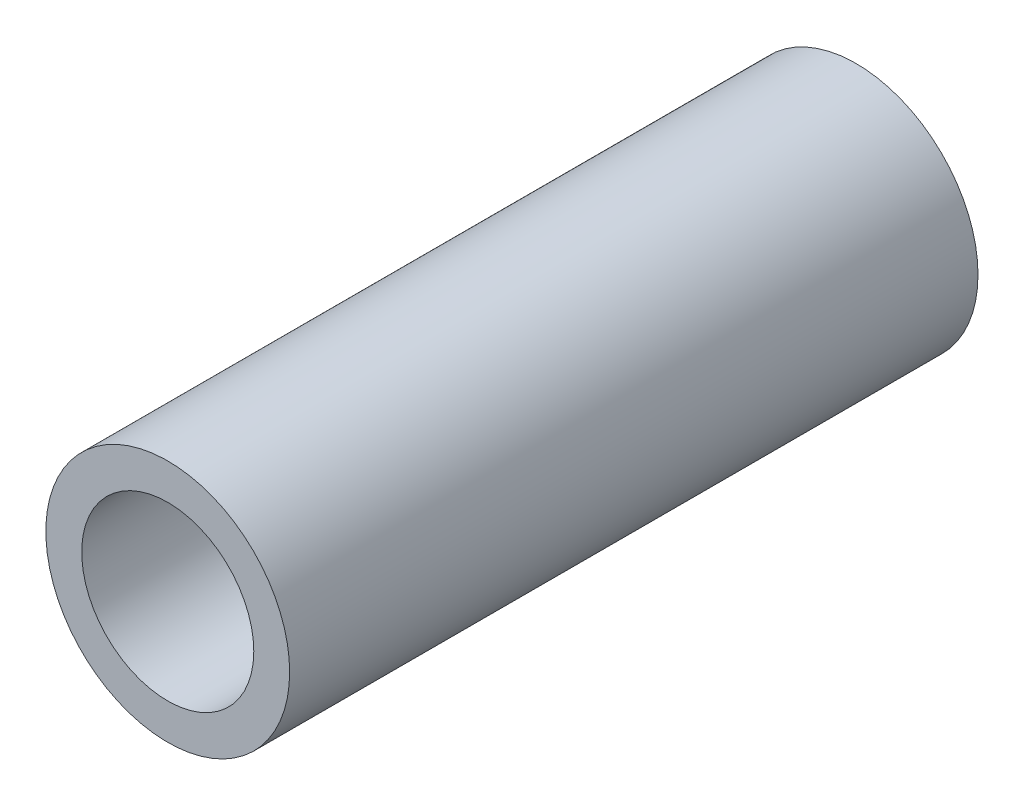
SolidWorks part; units mm, degrees
material "Silicon Rubber"
ref_plane "X-Y Datum" through (0, 0, 0) normal (0, 0, 1) x (1, 0, 0)
ref_plane "X-Z Datum" through (0, 0, 0) normal (0, 1, 0) x (1, 0, 0)
ref_plane "Y-Z Datum" through (0, 0, 0) normal (1, 0, 0) x (0, 0, -1)
sketch3d "3DSketch1"
  line L0 (0, 0, 0) -> (0, 0, 76.2)
  dimension "D1" = 76.2
sweep "Sweep1" add path "3DSketch1" circular profile diameter 26.9875 parameters "D3"=26.9875
sweep "Cut-Sweep1" cut path "3DSketch1<2>" circular profile diameter 19.05 parameters "D3"=19.05
sketch3d "3DSketch1<2>" same geometry as "3DSketch1"
sketch3d "3DSketch2"
  circle A0 centre (0, 0, 50.8) radius 9.525 construction
  circle A1 centre (0, 0, 25.4) radius 9.525 construction
  circle A2 centre (0, 0, 76.2) radius 13.4937 construction
  circle A3 centre (0, 0, 0) radius 9.525 construction
  point P4 (0, 0, 15.875)
  point P5 (0, 0, -9.525)
  point P8 (0, 0, 41.275)
  point P12 (0, 0, 89.6937)
  dimension "D1" = 25.4
  dimension "D2" = 25.4
